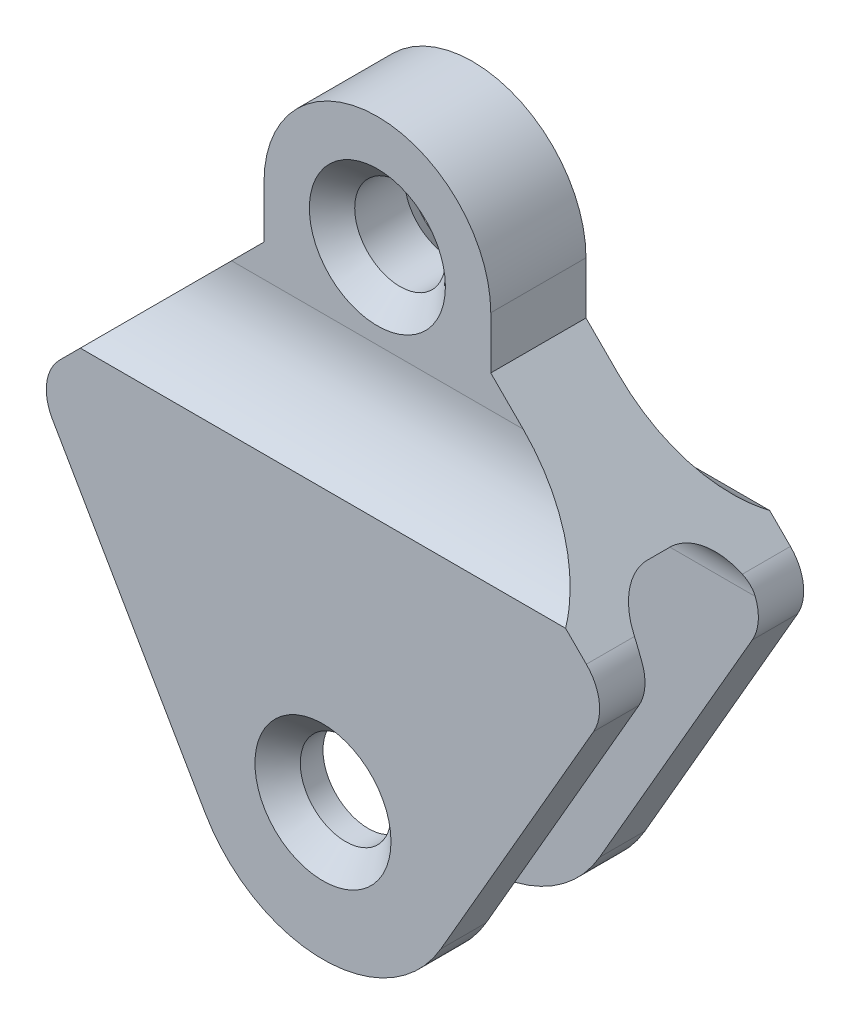
SolidWorks part; units mm, degrees
material "Plain Carbon Steel"
ref_plane "Front Plane" through (0, 0, 0) normal (0, 0, 1) x (1, 0, 0)
ref_plane "Top Plane" through (0, 0, 0) normal (0, 1, 0) x (1, 0, 0)
ref_plane "Right Plane" through (0, 0, 0) normal (1, 0, 0) x (0, 0, -1)
sketch "Sketch2" plane through (0, 0, 0) normal (0, 0, 1) x (1, 0, 0)
  line L0 (-25, 0) -> (-25, -11.4915)
  line L1 (-25, -11.4915) -> (-63.5085, -50)
  line L2 (-63.5085, -50) -> (-25.9808, -115)
  line L3 (63.5085, -50) -> (25.9808, -115)
  line L4 (25, -11.4915) -> (63.5085, -50)
  line L5 (25, 0) -> (25, -11.4915)
  line L6 (0, 25) -> (0, -116.5664) construction
  circle A0 centre (0, 0) radius 10
  arc A1 (25, 0) -> (-25, 0) centre (0, 0) ccw
  circle A2 centre (0, -100) radius 10
  arc A3 (-25.9808, -115) -> (25.9808, -115) centre (0, -100) ccw
  dimension "D1" = 25
  dimension "D2" = 30
  dimension "D3" = 20
  dimension "D4" = 20
  dimension "D5" = 90
  dimension "D6" = 60
  dimension "D7" = 100
  dimension "D8" = 50
extrude "Boss-Extrude2" add sketch "Sketch2" along normal blind 22.5
sketch "Sketch7" plane through (0, 0, 22.5) normal (0, 0, 1) x (1, 0, 0)
  line L0 (-25, -11.4915) -> (-53.5085, -40)
  line L1 (-25, -11.4915) -> (-63.5085, -50) construction
  line L2 (-53.5085, -40) -> (53.5085, -40)
  line L3 (63.5085, -50) -> (25, -11.4915) construction
  line L4 (53.5085, -40) -> (25, -11.4915)
  line L5 (25, -11.4915) -> (25, 0)
  line L6 (-25, -11.4915) -> (-25, 0)
  line L7 (0, 25) -> (-64.2161, 25) construction
  arc A0 (25, 0) -> (-25, 0) centre (0, 0) ccw
  dimension "D1" = 65
extrude "Cut-Extrude4" cut sketch "Sketch7" against normal blind 12
fillet "Fillet7" radius 25 1 edges at (0, -40, 10.5)
sketch "Sketch8" plane through (0, 0, 0) normal (0, 0, -1) x (-1, 0, 0)
  line L0 (-51.5085, -38) -> (51.5085, -38)
  line L1 (51.5085, -38) -> (63.5085, -50)
  line L2 (63.5085, -50) -> (25.9808, -115)
  line L3 (-63.5085, -50) -> (-25, -11.4915) construction
  line L4 (-63.5085, -50) -> (-25.9808, -115)
  line L5 (0, -130) -> (-53.5085, -130) construction
  line L7 (25, -11.4915) -> (63.5085, -50) construction
  line L8 (-51.5085, -38) -> (-63.5085, -50)
  arc A0 (-25.9808, -115) -> (25.9808, -115) centre (0, -100) ccw construction
  arc A1 (-25.9808, -115) -> (25.9808, -115) centre (0, -100) ccw
  dimension "D1" = 92
extrude "Cut-Extrude5" cut sketch "Sketch8" against normal blind 12.5
fillet "Fillet8" radius 10 1 edges at (0, -38, 12.5)
fillet "Fillet9" radius 10 2 edges at (-63.5085, -50, 17.5) (63.5085, -50, 17.5)
chamfer "Chamfer5" distance 5 angle 45 2 edges at (10, -100, 22.5) (10, 0, 10.5)
mirror "Mirror3" about plane through (0, -100, 0) normal (0, 0, 1) of bodies 109
